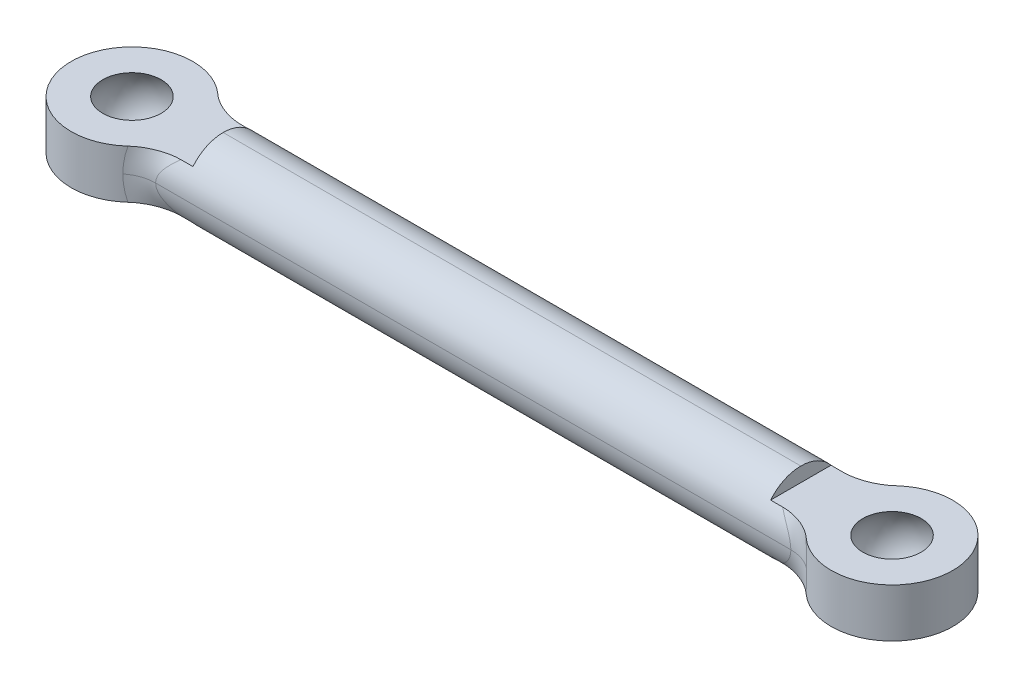
SolidWorks part; units mm, degrees
material "6061-T6 (SS)"
ref_plane "Front Plane" through (0, 0, 0) normal (0, 0, 1) x (1, 0, 0)
ref_plane "Top Plane" through (0, 0, 0) normal (0, 1, 0) x (1, 0, 0)
ref_plane "Right Plane" through (0, 0, 0) normal (1, 0, 0) x (0, 0, -1)
sketch "Sketch1" plane through (0, 0, 0) normal (0, 1, 0) x (1, 0, 0)
  line L0 (0, 0) -> (63.5, 0) construction
  line L1 (3.9139, -3.2385) -> (59.5861, -3.2385)
  line L2 (3.9139, 3.2385) -> (59.5861, 3.2385)
  line L3 (0, 3.2385) -> (63.5, 3.2385) construction
  line L4 (0, -3.2385) -> (63.5, -3.2385) construction
  arc A0 (59.5861, -3.2385) -> (59.5861, 3.2385) centre (63.5, 0) ccw
  arc A1 (3.9139, 3.2385) -> (3.9139, -3.2385) centre (0, 0) ccw
  dimension "D2" = 10.16
  dimension "D3" = 10.16
  dimension "D1" = 63.5
  dimension "D4" = 3.2385
  dimension "D5" = 3.2385
extrude "Boss-Extrude1" add sketch "Sketch1" along normal blind 6.477
sketch "Sketch2" plane through (0, 0, 0) normal (0, 0, 1) x (1, 0, 0)
  line L0 (-5.08, 3.2385) -> (68.58, 3.2385) construction
  line L1 (-5.08, 6.477) -> (-5.08, 0) construction
  line L2 (68.58, 0) -> (68.58, 6.477) construction
  line L3 (3.9139, 6.477) -> (59.5861, 6.477) construction
  line L4 (-5.08, 6.477) -> (7.62, 6.477)
  line L5 (-5.08, 6.477) -> (-5.08, 5.2705)
  line L6 (-5.08, 5.2705) -> (7.62, 5.2705)
  line L7 (7.62, 6.477) -> (7.62, 5.2705)
  line L8 (7.62, 0) -> (7.62, 1.2065)
  line L9 (-5.08, 1.2065) -> (7.62, 1.2065)
  line L10 (-5.08, 0) -> (-5.08, 1.2065)
  line L11 (-5.08, 0) -> (7.62, 0)
  line L12 (31.75, 3.2385) -> (31.75, 0) construction
  line L13 (68.58, 0) -> (55.88, 0)
  line L14 (68.58, 0) -> (68.58, 1.2065)
  line L15 (68.58, 1.2065) -> (55.88, 1.2065)
  line L16 (55.88, 0) -> (55.88, 1.2065)
  line L17 (55.88, 6.477) -> (55.88, 5.2705)
  line L18 (68.58, 5.2705) -> (55.88, 5.2705)
  line L19 (68.58, 6.477) -> (68.58, 5.2705)
  line L20 (68.58, 6.477) -> (55.88, 6.477)
  dimension "D1" = 2.032
  dimension "D2" = 12.7
  dimension "D3" = 0
extrude "Cut-Extrude1" cut sketch "Sketch2" against normal through all and the other way through all
fillet "Fillet1" radius 3.2385 4 edges at (31.75, 0, -3.2385) (31.75, 0, 3.2385) (31.75, 6.477, 3.2385) (31.75, 6.477, -3.2385)
fillet "Fillet2" radius 3.2385 8 edges at (4.0252, 2.2982, -3.099) (59.4224, 2.0948, -3.0298) (4.0776, 2.0948, 3.0298) (59.4748, 2.2982, 3.099) (4.0776, 4.3822, -3.0298) (59.4748, 4.1788, -3.099) (4.0252, 4.1788, 3.099) (59.4224, 4.3822, 3.0298)
ref_plane "Plane1" through (0, 3.2385, 0) normal (0, -1, 0) x (-1, 0, 0)
sketch "Sketch3" plane through (0, 3.2385, 0) normal (0, -1, 0) x (-1, 0, 0)
  line L0 (0, 3.175) -> (0, -3.175)
  circle A0 centre (0, 0) radius 3.175
  dimension "D1" = 6.35
sketch "Sketch4" [suppressed] plane through (0, 3.2385, 0) normal (0, -1, 0) x (-1, 0, 0)
  line L0 (0, 0) -> (0, 18.2322) construction
revolve "Cut-Revolve8" cut sketch "Sketch3" angle 360 about L0 region at (-1.3475, 3.2385, 0)
ref_plane "Plane2" [suppressed] through (31.75, 0, 0) normal (-1, 0, 0) x (0, 0, 1)
mirror "Mirror1" about plane through (31.75, 0, 0) normal (-1, 0, 0) of "Cut-Revolve8"
equation "\"D3@Sketch1\"=\"D2@Sketch1\""
